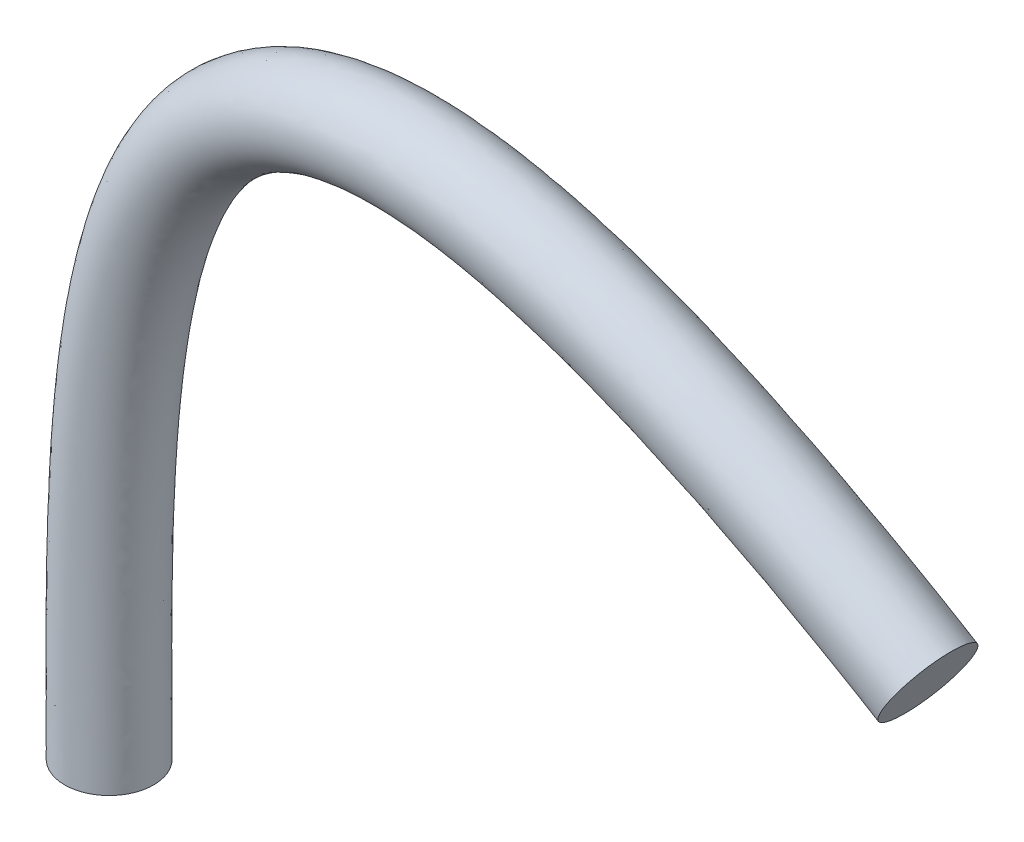
SolidWorks part; units mm, degrees
ref_plane "Спереди" through (0, 0, 0) normal (0, 0, 1) x (1, 0, 0)
ref_plane "Сверху" through (0, 0, 0) normal (0, 1, 0) x (1, 0, 0)
ref_plane "Справа" through (0, 0, 0) normal (1, 0, 0) x (0, 0, -1)
sketch "Эскиз1" plane through (0, 0, 0) normal (0, 1, 0) x (1, 0, 0)
  circle A0 centre (0, 0) radius 4
  dimension "D1" = 8
sketch "Эскиз2" plane through (0, 0, 0) normal (0, 0, 1) x (1, 0, 0)
  spline S0 degree 3 poles (0, 0) (-0.0009, 35.4127) (-3.0818, 88.8167) (73.5333, 42.7312) knots 0 0 0 0 1 1 1 1
sweep "По траектории1" add profiles "Эскиз1" path "Эскиз2"
